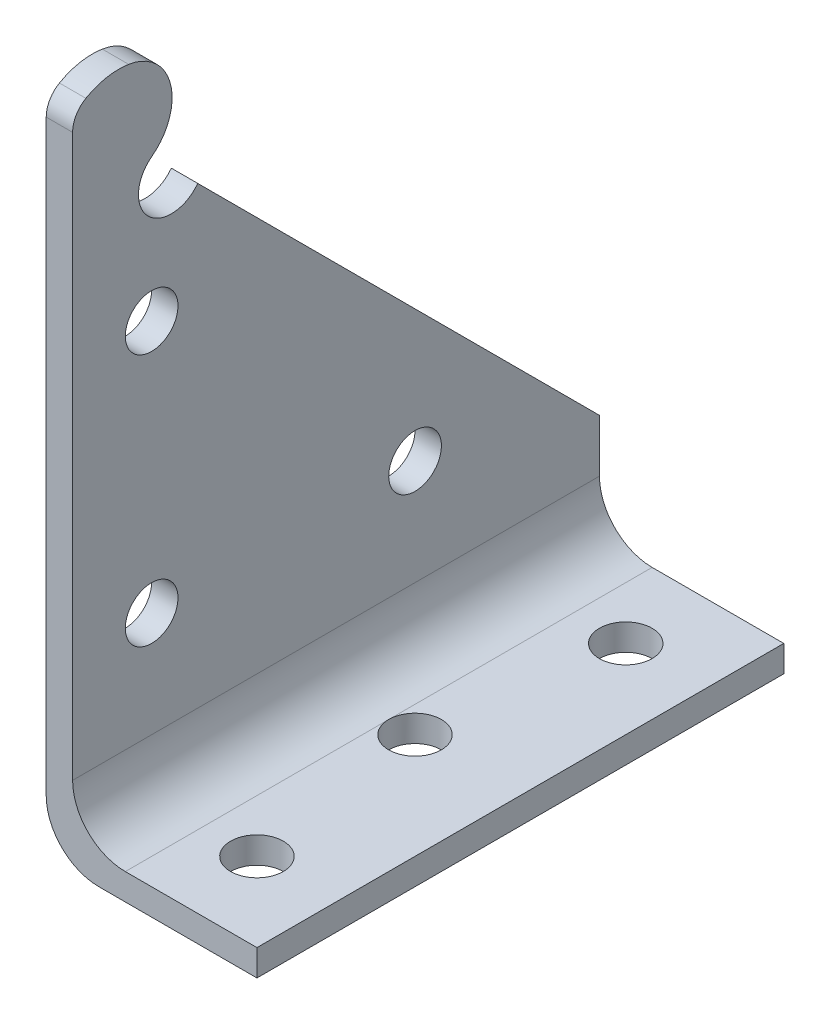
SolidWorks part; units mm, degrees
material "Alloy Steel"
ref_plane "Front Plane" through (0, 0, 0) normal (0, 0, 1) x (1, 0, 0)
ref_plane "Top Plane" through (0, 0, 0) normal (0, 1, 0) x (1, 0, 0)
ref_plane "Right Plane" through (0, 0, 0) normal (1, 0, 0) x (0, 0, -1)
sketch "Sketch1" plane through (0, 0, 0) normal (0, 0, 1) x (1, 0, 0)
  line L0 (0, 0) -> (0, 81.28)
  line L1 (0, 81.28) -> (3.1826, 81.28)
  line L2 (3.1826, 81.28) -> (3.1826, 3.175)
  line L3 (3.1826, 3.175) -> (25.4, 3.175)
  line L4 (25.4, 3.175) -> (25.4, 0)
  line L5 (25.4, 0) -> (0, 0)
  dimension "D1" = 3.175
  dimension "D2" = 3.1826
  dimension "D3" = 81.28
  dimension "D4" = 25.4
extrude "Boss-Extrude1" add sketch "Sketch1" along normal mid plane 63.5
fillet "Fillet1" radius 6.35 1 edges at (0, 0, 0)
fillet "Fillet2" radius 6.35 1 edges at (3.1826, 3.175, 0)
sketch "Sketch2" plane through (3.1826, 0, 0) normal (1, 0, 0) x (0, 0, -1)
  line L0 (-31.75, 0) -> (31.75, 0) construction
  line L1 (-31.75, 9.525) -> (-31.75, 81.28) construction
  line L2 (31.75, 15.875) -> (-16.6695, 64.2945)
  line L3 (-31.75, 81.28) -> (31.75, 81.28) construction
  line L4 (31.75, 9.525) -> (31.75, 81.28) construction
  line L7 (-31.75, 3.175) -> (31.75, 3.175) construction
  line L8 (-16.6695, 64.2945) -> (-31.75, 79.375) construction
  line L9 (-31.75, 9.525) -> (31.75, 9.525) construction
  circle A0 centre (-22.225, 22.225) radius 3.175
  circle A1 centre (9.525, 22.225) radius 3.175
  circle A2 centre (-22.225, 52.705) radius 3.175
  arc A3 (-22.2255, 69.8505) -> (-16.6695, 64.2945) centre (-19.845, 66.675) ccw
  arc A4 (-22.2255, 69.8505) -> (-24.9925, 80.8837) centre (-25.9255, 74.7862) ccw
  arc A5 (-26.195, 80.9752) -> (-24.9925, 80.8837) centre (-26.195, 73.025) cw
  arc A6 (-26.195, 80.9752) -> (-30.154, 79.9194) centre (-26.195, 73.025) ccw
  arc A7 (-30.154, 79.9194) -> (-31.75, 77.1624) centre (-28.5709, 77.1624) ccw
  point P19 (-26.195, 73.025)
  point P24 (-26.195, 80.9752)
  line M1 (-31.75, 81.28) -> (-31.75, 9.525)
  line M3 (31.75, 9.525) -> (31.75, 81.28)
  line M4 (31.75, 81.28) -> (-31.75, 81.28)
  dimension "D1" = 6.35
  dimension "D9" = 7.9375
  dimension "D13" = 80.9752
  dimension "D15" = 3.1791
  dimension "D2" = 22.225
  dimension "D3" = 9.525
  dimension "D4" = 31.75
  dimension "D5" = 30.48
  dimension "D6" = 66.675
  dimension "D7" = 45
  dimension "D8" = 12.7
  dimension "D10" = 11.905
  dimension "D11" = 5.555
  dimension "D12" = 73.025
extrude "Cut-Extrude1" cut sketch "Sketch2" against normal through all contours L8 L2 A7 A6 A5 A4 M3 M4 M1 | A3 L8 | A7 L8 M1 | A2 | A0 | A1 region at (3.1826, 58.8685, -11.1907) region at (3.1826, 65.6957, 20.8244) region at (3.1826, 78.637, 31.5962) region at (3.1826, 22.225, 22.225) region at (3.1826, 22.225, -9.525) region at (3.1826, 52.705, 22.225)
sketch "Sketch3" plane through (0, 3.175, 0) normal (0, 1, 0) x (1, 0, 0)
  line L0 (25.4, -31.75) -> (25.4, 31.75) construction
  line L1 (25.4, -31.75) -> (9.5326, -31.75) construction
  line L2 (25.4, 31.75) -> (9.5326, 31.75) construction
  circle A0 centre (15.875, -22.225) radius 3.175
  circle A1 centre (12.7, 0) radius 3.175
  circle A2 centre (15.875, 22.225) radius 3.175
  dimension "D1" = 6.35
  dimension "D2" = 9.525
  dimension "D3" = 12.7
  dimension "D4" = 9.525
  dimension "D5" = 31.75
  dimension "D6" = 9.525
extrude "Cut-Extrude2" cut sketch "Sketch3" against normal through all
